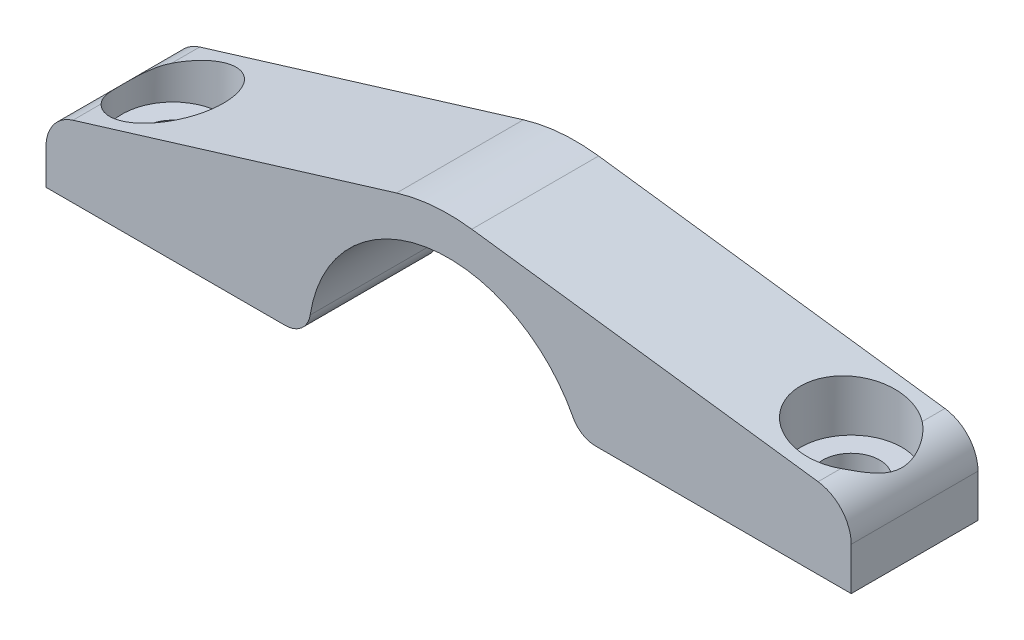
SolidWorks part; units mm, degrees
material "Сплав 2024"
ref_plane "Спереди" through (0, 0, 0) normal (0, 0, 1) x (1, 0, 0)
ref_plane "Сверху" through (0, 0, 0) normal (0, 1, 0) x (1, 0, 0)
ref_plane "Справа" through (0, 0, 0) normal (1, 0, 0) x (0, 0, -1)
sketch "Эскиз1" plane through (0, 0, 0) normal (0, 0, 1) x (1, 0, 0)
  line L0 (-50.7044, 0) -> (94.5195, 0) construction
  line L1 (0, 39.6279) -> (0, -47.9421) construction
  line L2 (-31.75, 5) -> (-4.1012, 13.4381)
  line L4 (-31.75, 5) -> (-31.75, 0)
  line L5 (-31.75, 0) -> (-11.05, 0)
  line L6 (31.75, 10) -> (31.75, 4)
  line L7 (-31.75, 5) -> (17.9945, 5) construction
  line L8 (-31.75, 0) -> (31.75, 10) construction
  line L9 (31.75, 10) -> (1.8299, 13.9303)
  line L10 (46.3702, 4) -> (-24.3242, 4) construction
  line L11 (31.75, 4) -> (10.3006, 4)
  arc A0 (-11.05, 0) -> (10.3006, 4) centre (0, 0) cw
  arc A1 (-4.1012, 13.4381) -> (1.8299, 13.9303) centre (0, 0) cw
  point P10 (0, 5)
  dimension "D1" = 11.05
  dimension "D2" = 3
  dimension "D3" = 63.5
  dimension "D4" = 5
  dimension "D5" = 31.75
  dimension "D6" = 4
  dimension "D7" = 6
extrude "Бобышка-Вытянуть1" add sketch "Эскиз1" along normal blind 10
fillet "Скругление1" [suppressed] radius 3
ref_plane "Плоскость1" through (0, 7, 0) normal (0, 1, 0) x (1, 0, 0)
sketch "Эскиз2" plane through (0, 7, 0) normal (0, 1, 0) x (1, 0, 0)
  line L0 (-31.75, -5) -> (-11.05, -5) construction
  line L1 (-31.75, -10) -> (-31.75, 0) construction
  line L2 (-11.05, -10) -> (-11.05, 0) construction
  line L3 (-26.75, -10) -> (-26.75, 0) construction
  dimension "D1" = 5
hole_wizard "Цековка для винта с внутренним шестигранником M42" positions "Эскиз6" profile "Эскиз5" counterbore size "M4" standard "Ansi Metric" end condition through all
sketch "Эскиз6" plane through (0, 7, 0) normal (0, 1, 0) x (1, 0, 0)
  line L0 (-31.75, -5) -> (-11.05, -5) construction
  line L1 (-26.75, -10) -> (-26.75, 0) construction
  point P0 (-26.75, -5)
sketch "Эскиз5" plane through (-26.75, 7, 5) normal (1, 0, 0) x (0, 0, -1)
  line L0 (0, 0) -> (0, 7.05)
  line L1 (0, 7.05) -> (2.25, 7.05)
  line L3 (2.25, 7.05) -> (2.25, 4)
  line L4 (2.25, 4) -> (4, 4)
  line L5 (4, 4) -> (4, 0)
  line L7 (4, 0) -> (0, 0)
  line L11 (0, -6.35) -> (0, 107.95) construction
  dimension "Диаметр сквозного отверстия" = 4.5
  dimension "Глубина сквозного отверстия" = 7.05
  dimension "Диаметр цековки" = 8
  dimension "Глубина цековки" = 4
hole_wizard "Цековка для винта с внутренним шестигранником M43" positions "Эскиз8" profile "Эскиз7" counterbore size "M4" standard "Ansi Metric" end condition through all
sketch "Эскиз8" plane through (0, 7, 0) normal (0, 1, 0) x (1, 0, 0)
  point P0 (-26.75, -5)
sketch "Эскиз7" plane through (-26.75, 7, 5) normal (1, 0, 0) x (0, 0, 1)
  line L0 (0, 0) -> (0, 7)
  line L1 (0, 7) -> (2.25, 7)
  line L3 (2.25, 7) -> (2.25, 4)
  line L4 (2.25, 4) -> (4, 4)
  line L5 (4, 4) -> (4, 0)
  line L7 (4, 0) -> (0, 0)
  line L11 (0, -6.35) -> (0, 107.95) construction
  dimension "Диаметр сквозного отверстия" = 4.5
  dimension "Глубина сквозного отверстия" = 7
  dimension "Диаметр цековки" = 8
  dimension "Глубина цековки" = 4
ref_plane "Плоскость2" through (0, 11, 0) normal (0, -1, 0) x (-1, 0, 0)
sketch "Эскиз9" plane through (0, 11, 0) normal (0, -1, 0) x (-1, 0, 0)
  line L0 (-31.75, -5) -> (-10.3006, -5) construction
  line L1 (-31.75, -10) -> (-31.75, 0) construction
  line L2 (-10.3006, -10) -> (-10.3006, 0) construction
  line L3 (-26.75, 0) -> (-26.75, -10) construction
  dimension "D1" = 5
hole_wizard "Цековка для винта с внутренним шестигранником M44" positions "Эскиз11" profile "Эскиз10" counterbore size "M4" standard "Ansi Metric" end condition through all
sketch "Эскиз11" plane through (0, 11, 0) normal (0, -1, 0) x (-1, 0, 0)
  line L0 (-26.75, 0) -> (-26.75, -10) construction
  line L1 (-31.75, -5) -> (-10.3006, -5) construction
  point P0 (-26.75, -5)
sketch "Эскиз10" plane through (26.75, 11, 5) normal (1, 0, 0) x (0, 0, 1)
  line L0 (0, 0) -> (0, 11)
  line L1 (0, 11) -> (2.25, 11)
  line L3 (2.25, 11) -> (2.25, 4)
  line L4 (2.25, 4) -> (4, 4)
  line L5 (4, 4) -> (4, 0)
  line L7 (4, 0) -> (0, 0)
  line L11 (0, -6.35) -> (0, 107.95) construction
  dimension "Диаметр сквозного отверстия" = 4.5
  dimension "Глубина сквозного отверстия" = 11
  dimension "Диаметр цековки" = 8
  dimension "Глубина цековки" = 4
hole_wizard "Цековка для винта с внутренним шестигранником M45" positions "Эскиз13" profile "Эскиз12" counterbore size "M4" standard "Ansi Metric" end condition through all
sketch "Эскиз13" plane through (0, 11, 0) normal (0, -1, 0) x (-1, 0, 0)
  line L0 (-31.75, -5) -> (-10.3006, -5) construction
  line L1 (-26.75, 0) -> (-26.75, -10) construction
  point P0 (-26.75, -5)
sketch "Эскиз12" plane through (26.75, 11, 5) normal (1, 0, 0) x (0, 0, -1)
  line L0 (0, 0) -> (0, 3.05)
  line L1 (0, 3.05) -> (2.25, 3.05)
  line L3 (2.25, 3.05) -> (2.25, 4)
  line L4 (2.25, 4) -> (4, 4)
  line L5 (4, 4) -> (4, 0)
  line L7 (4, 0) -> (0, 0)
  line L11 (0, -6.35) -> (0, 107.95) construction
  dimension "Диаметр сквозного отверстия" = 4.5
  dimension "Глубина сквозного отверстия" = 3.05
  dimension "Диаметр цековки" = 8
  dimension "Глубина цековки" = 4
fillet "Скругление4" radius 2 2 edges at (10.3006, 4, 5) (-11.05, 0, 5)
fillet "Скругление2" radius 3 2 edges at (-31.75, 5, 5) (31.75, 10, 5)
fillet "Скругление3" [suppressed] radius 0.5
